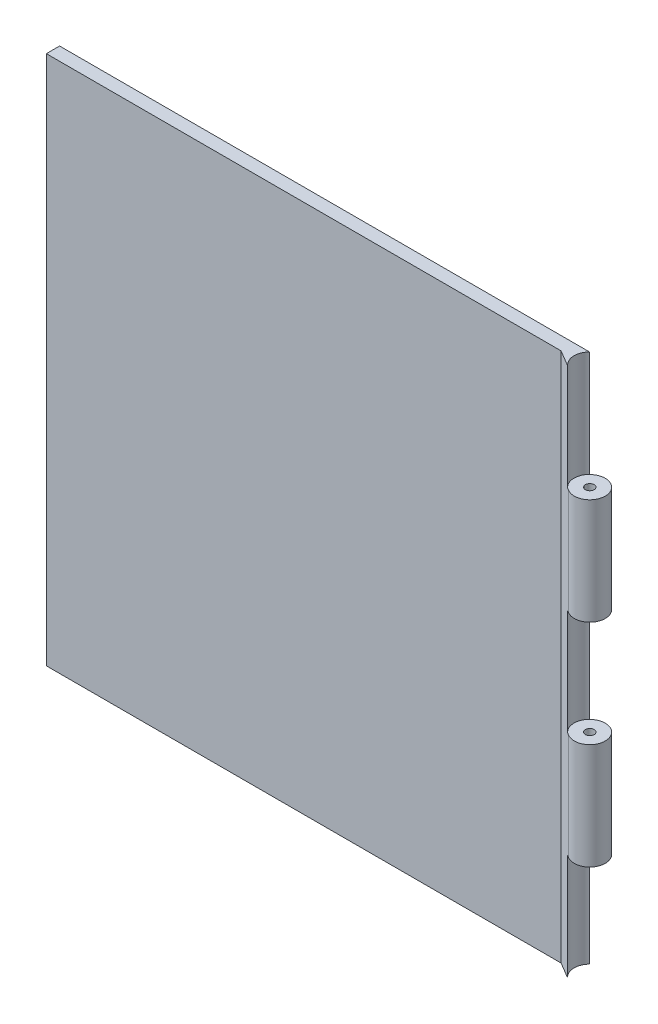
SolidWorks part; units mm, degrees
ref_plane "Plano frontal" through (0, 0, 0) normal (0, 0, 1) x (1, 0, 0)
ref_plane "Plano superior" through (0, 0, 0) normal (0, 1, 0) x (1, 0, 0)
ref_plane "Plano direito" through (0, 0, 0) normal (1, 0, 0) x (0, 0, -1)
sketch "Esboço1" plane through (0, 0, 0) normal (0, 0, 1) x (1, 0, 0)
  line L1 (-60, -60) -> (60, -60)
  line L2 (-60, -60) -> (-60, 60)
  line L3 (-60, 60) -> (60, 60)
  line L4 (60, -60) -> (60, 60)
  line L5 (-60, -60) -> (60, 60) construction
  line L6 (-60, 60) -> (60, -60) construction
  point P0 (0, 0)
  dimension "D1" = 120
  dimension "D2" = 120
extrude "Ressalto-extrusão1" add sketch "Esboço1" along normal blind 3
sketch "Esboço2" plane through (0, 0, 0) normal (0, 0, -1) x (-1, 0, 0)
  line L8 (-56.4, 56.4) -> (-56.4, -56.4)
  line L9 (-56.4, -56.4) -> (56.4, -56.4)
  line L10 (56.4, -56.4) -> (56.4, 56.4)
  line L11 (56.4, 56.4) -> (-56.4, 56.4)
  line L12 (-56.4, 56.4) -> (-56.4, -56.4)
  line L13 (-56.4, -56.4) -> (56.4, -56.4)
  line L14 (56.4, -56.4) -> (56.4, 56.4)
  line L15 (56.4, 56.4) -> (-56.4, 56.4)
  dimension "D1" = 3.6
extrude "Ressalto-extrusão2" add sketch "Esboço2" along normal blind 2
sketch "Esboço3" plane through (0, 0, -2) normal (0, 0, -1) x (-1, 0, 0)
  line L8 (54.4, 54.4) -> (-54.4, 54.4)
  line L9 (-54.4, 54.4) -> (-54.4, -54.4)
  line L10 (-54.4, -54.4) -> (54.4, -54.4)
  line L11 (54.4, -54.4) -> (54.4, 54.4)
  line L12 (54.4, 54.4) -> (-54.4, 54.4)
  line L13 (-54.4, 54.4) -> (-54.4, -54.4)
  line L14 (-54.4, -54.4) -> (54.4, -54.4)
  line L15 (54.4, -54.4) -> (54.4, 54.4)
  dimension "D1" = 2
extrude "Corte-extrusão1" cut sketch "Esboço3" against normal blind 2
chamfer "Chanfro1" distance 0.5 angle 45 4 edges at (-56.4, 0, -2) (0, -56.4, -2) (56.4, 0, -2) (0, 56.4, -2)
sketch "Esboço5" plane through (0, 0, 0) normal (0, 1, 0) x (1, 0, 0)
  line L0 (48.3486, 0) -> (60, 0) construction
  line L1 (60, 0) -> (60, 10.0434) construction
  line L2 (60, 10.0434) -> (48.3486, 10.0434) construction
  line L3 (48.3486, 10.0434) -> (48.3486, 0) construction
  line L4 (60, -3) -> (60, 0) construction
  line L5 (62.4749, -2.4749) -> (65.9749, -2.4749) construction
  line L6 (62.4749, -2.4749) -> (60, 0) construction
  line L7 (60.6913, -5.4863) -> (56.4933, -3)
  line L8 (60, -3) -> (-60, -3) construction
  line L9 (56.4933, -3) -> (59.0145, -3)
  arc A0 (60.6913, -5.4863) -> (59.0145, -3) centre (62.4749, -2.4749) ccw
  point P10 (61.0513, -5.6723)
  point P15 (61.0513, -5.6723)
  point P16 (0, 0)
  point P17 (0, 0)
  point P18 (56.4933, -3)
  point P19 (0, 0)
  dimension "D1" = 135
  dimension "D2" = 3.5
extrude "Ressalto-extrusão3" add sketch "Esboço5" along normal mid plane 120
sketch "Esboço6" plane through (0, 60, 0) normal (0, 1, 0) x (1, 0, 0)
  circle A0 centre (62.4749, -2.4749) radius 3.55
  dimension "D1" = 7.1
extrude "Corte-extrusão2" cut sketch "Esboço6" against normal blind 24
ref_plane "Plano1" through (0, 12, 0) normal (0, 1, 0) x (1, 0, 0)
sketch "Esboço7" plane through (0, 12, 0) normal (0, 1, 0) x (1, 0, 0)
  circle A0 centre (62.4749, -2.4749) radius 3.55
extrude "Corte-extrusão3" cut sketch "Esboço7" against normal blind 24
ref_plane "Plano2" through (0, -36, 0) normal (0, 1, 0) x (1, 0, 0)
sketch "Esboço9" plane through (0, -36, 0) normal (0, 1, 0) x (1, 0, 0)
  circle A0 centre (62.4749, -2.4749) radius 3.55
extrude "Corte-extrusão4" cut sketch "Esboço9" against normal blind 24
sketch "Esboço10" plane through (0, 60, 0) normal (0, 1, 0) x (1, 0, 0)
  circle A0 centre (62.4749, -2.4749) radius 1
extrude "Corte-extrusão5" cut sketch "Esboço10" against normal through all both and the other way through all
ref_plane "Plano3" through (0, 12, 0) normal (0, 1, 0) x (1, 0, 0)
sketch "Esboço11" plane through (0, 12, 0) normal (0, 1, 0) x (1, 0, 0)
  line L0 (-60.6256, -2.4492) -> (-57.2551, 0.3085)
  line L1 (-57.2551, 0.3085) -> (-60.6256, 0.3085)
  line L2 (-60.6256, 0.3085) -> (-60.6256, -2.4492)
extrude "Corte-extrusão6" cut sketch "Esboço11" against normal blind 24
sketch "Esboço14" plane through (0, 0, 0) normal (0, 0, -1) x (-1, 0, 0)
  line L0 (54.4, -54.4) -> (54.4, 54.4) construction
  line L1 (49.4, 5) -> (54.4, 5)
  line L2 (54.4, -54.4) -> (54.4, 54.4) construction
  line L3 (54.4, 5) -> (54.4, -5)
  line L4 (54.4, -5) -> (49.4, -5)
  arc A0 (49.4, 5) -> (49.4, -5) centre (49.4, 0) ccw
  dimension "D1" = 10
extrude "Ressalto-extrusão13" add sketch "Esboço14" along normal blind 3
fillet "Filete1" radius 3 3 edges at (-51.9, 5, 0) (-51.9, -5, 0) (-44.4, 0, 0)
